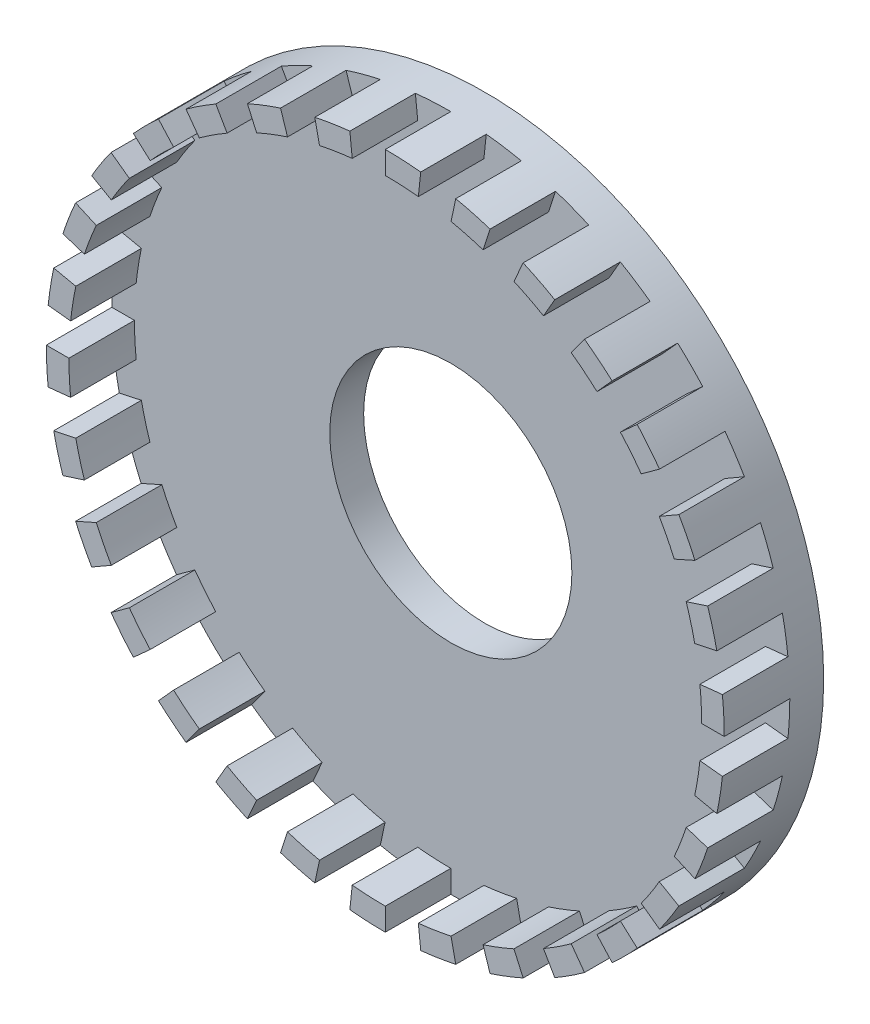
SolidWorks part; units mm, degrees
material "ABS"
ref_plane "Front Plane" through (0, 0, 0) normal (0, 0, 1) x (1, 0, 0)
ref_plane "Top Plane" through (0, 0, 0) normal (0, 1, 0) x (1, 0, 0)
ref_plane "Right Plane" through (0, 0, 0) normal (1, 0, 0) x (0, 0, -1)
ref_axis "Axis1" through (0, 0, -106.6398) along (0, 0, 1)
sketch "Sketch1" plane through (0, 0, 0) normal (0, 0, 1) x (1, 0, 0)
  circle A0 centre (0, 0) radius 10.7156
  circle A1 centre (0, 0) radius 30
extrude "Boss-Extrude1" add sketch "Sketch1" along normal blind 3
sketch "Sketch2" plane through (0, 0, 3) normal (0, 0, 1) x (1, 0, 0)
  line L0 (0, 30) -> (0, 28)
  line L1 (2.9268, 27.8466) -> (3.1359, 29.8357)
  arc A0 (0, 30) -> (3.1359, 29.8357) centre (0, 0) cw
  circle A1 centre (0, 0) radius 30 construction
  arc A2 (2.9268, 27.8466) -> (0, 28) centre (0, 0) ccw
  dimension "D1" = 2
extrude "Boss-Extrude2" add sketch "Sketch2" along normal blind 5.8
pattern_circular "CirPattern1" count 30 every 12 about axis through (0, 0, -106.6398) along (0, 0, 1) of "Boss-Extrude2"
